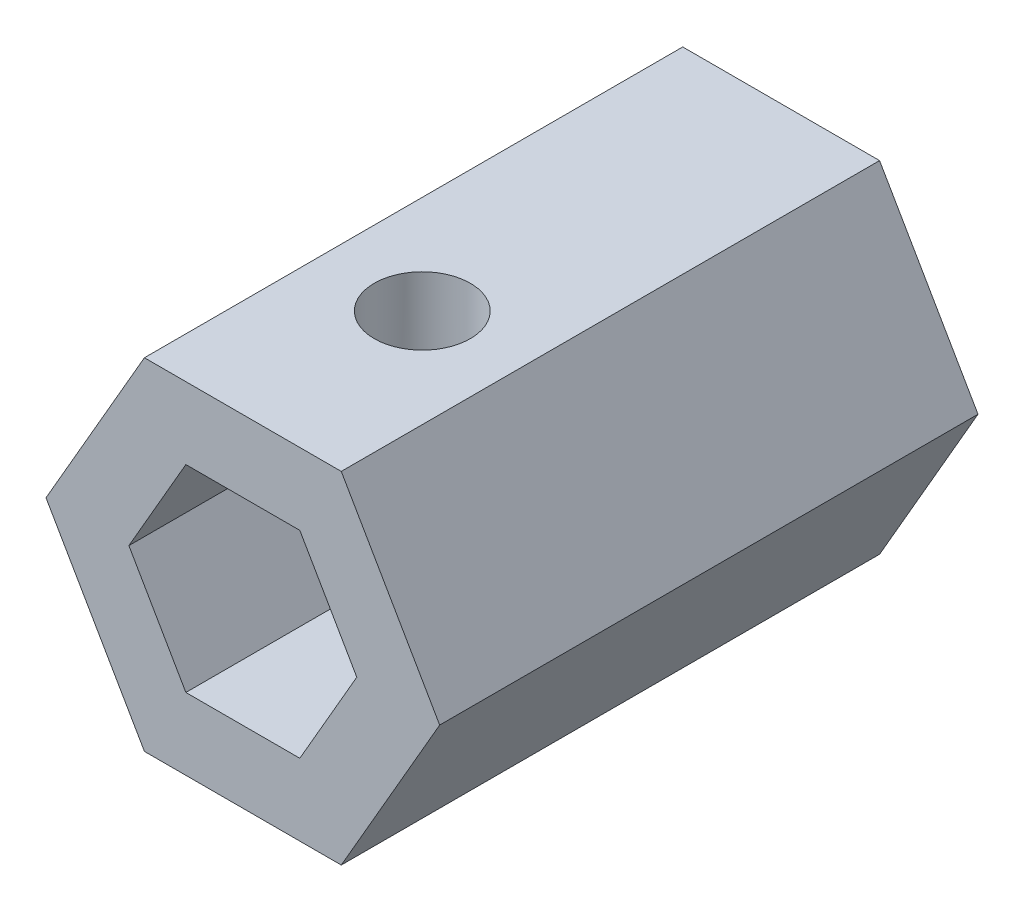
SolidWorks part; units mm, degrees
material "ABS"
ref_plane "Front Plane" through (0, 0, 0) normal (0, 0, 1) x (1, 0, 0)
ref_plane "Top Plane" through (0, 0, 0) normal (0, 1, 0) x (1, 0, 0)
ref_plane "Right Plane" through (0, 0, 0) normal (1, 0, 0) x (0, 0, -1)
sketch "Sketch1" plane through (0, 0, 0) normal (0, 0, 1) x (1, 0, 0)
  line L0 (6.9657, 12.065) -> (-6.9657, 12.065)
  line L1 (4.0328, -6.985) -> (8.0656, 0)
  line L2 (8.0656, 0) -> (4.0328, 6.985)
  line L3 (4.0328, 6.985) -> (-4.0328, 6.985)
  line L4 (-4.0328, 6.985) -> (-8.0656, 0)
  line L5 (-8.0656, 0) -> (-4.0328, -6.985)
  line L6 (-4.0328, -6.985) -> (4.0328, -6.985)
  line L7 (-6.9657, 12.065) -> (-13.9315, 0)
  line L8 (-13.9315, 0) -> (-6.9657, -12.065)
  line L9 (-6.9657, -12.065) -> (6.9657, -12.065)
  line L10 (6.9657, -12.065) -> (13.9315, 0)
  line L11 (13.9315, 0) -> (6.9657, 12.065)
  circle A0 centre (0, 0) radius 6.985 construction
  point P16 (0, 0)
  dimension "D1" = 13.97
  dimension "D2" = 5.08
extrude "Boss-Extrude1" add sketch "Sketch1" along normal blind 2.54 contours L5 L6 L1 L2 L3 L4 | L10 L11 L0 L7 L8 L9 L6 L5 L4 L3 L2 L1 region at (10.1294, 5.8482, 0) region at (0, 0, 0)
sketch "Sketch2" plane through (0, 0, 2.54) normal (0, 0, 1) x (1, 0, 0)
  point P0 (0, 0)
  point P1 (-17.2019, 6.9381)
hole_wizard "CSK for #8 Flat Head Machine Screw (100)1" positions "Sketch2" profile "Sketch3" countersink size "#8" standard "ANSI Inch" end condition through all
sketch "Sketch3" plane through (0, 0, 2.54) normal (1, 0, 0) x (0, -1, 0)
  line L0 (0, 0) -> (0, 2.54)
  line L1 (0, 2.54) -> (2.2479, 2.54)
  line L2 (2.2479, 2.54) -> (2.2479, 1.6518)
  line L3 (2.2479, 1.6518) -> (4.2164, 0)
  line L5 (4.2164, 0) -> (0, 0)
  line L6 (-2.2479, 1.6518) -> (-4.2164, 0) construction
  line L11 (0, -6.35) -> (0, 107.95) construction
  dimension "Thru Hole Dia." = 4.4958
  dimension "Thru Hole Depth" = 2.54
  dimension "Near C'Sink Dia." = 8.4328
  dimension "Near C'Sink Angle" = 100
extrude "Boss-Extrude2" add sketch "Sketch1<4>" along normal blind 25.4
sketch "Sketch1<4>" plane through (0, 0, 0) normal (0, 0, 1) x (1, 0, 0) same geometry as "Sketch1"
sketch "Sketch4" plane through (0, 12.065, 0) normal (0, 1, 0) x (1, 0, 0)
  line L0 (0, 0) -> (0, -25.4) construction
  line L1 (6.9657, 0) -> (-6.9657, 0) construction
  line L2 (6.9657, -25.4) -> (-6.9657, -25.4) construction
  point P6 (0, -12.7)
hole_wizard "M8x1.25 Tapped Hole1" positions "Sketch4" profile "Sketch5" tap size "M8x1.25" standard "ANSI Metric" end condition through all
sketch "Sketch5" plane through (0, 12.065, 12.7) normal (1, 0, 0) x (0, 0, 1)
  line L0 (0, 0) -> (0, 24.13)
  line L1 (0, 24.13) -> (3.4, 24.13)
  line L2 (3.4, 24.13) -> (3.4, 0)
  line L5 (3.4, 0) -> (0, 0)
  line L11 (0, -6.35) -> (0, 107.95) construction
  dimension "Thru Tap Drill Dia." = 6.8
  dimension "Thru Tap Drill Depth" = 24.13
cosmetic thread "Hole Thread2" parameters "D2"=8
sketch "Sketch6" plane through (0, 0, 0) normal (0, 0, -1) x (-1, 0, 0)
  line L6 (-13.9315, 0) -> (-6.9657, -12.065)
  line L7 (-6.9657, -12.065) -> (6.9657, -12.065)
  line L8 (6.9657, -12.065) -> (13.9315, 0)
  line L9 (13.9315, 0) -> (6.9657, 12.065)
  line L10 (6.9657, 12.065) -> (-6.9657, 12.065)
  line L11 (-6.9657, 12.065) -> (-13.9315, 0)
  line L12 (-13.9315, 0) -> (-6.9657, -12.065)
  line L13 (-6.9657, -12.065) -> (6.9657, -12.065)
  line L14 (6.9657, -12.065) -> (13.9315, 0)
  line L15 (13.9315, 0) -> (6.9657, 12.065)
  line L16 (6.9657, 12.065) -> (-6.9657, 12.065)
  line L17 (-6.9657, 12.065) -> (-13.9315, 0)
  circle A0 centre (0, 0) radius 6.25
  dimension "D2" = 12.5
  dimension "D1" = 0
extrude "Boss-Extrude3" add sketch "Sketch6" along normal blind 12.7
